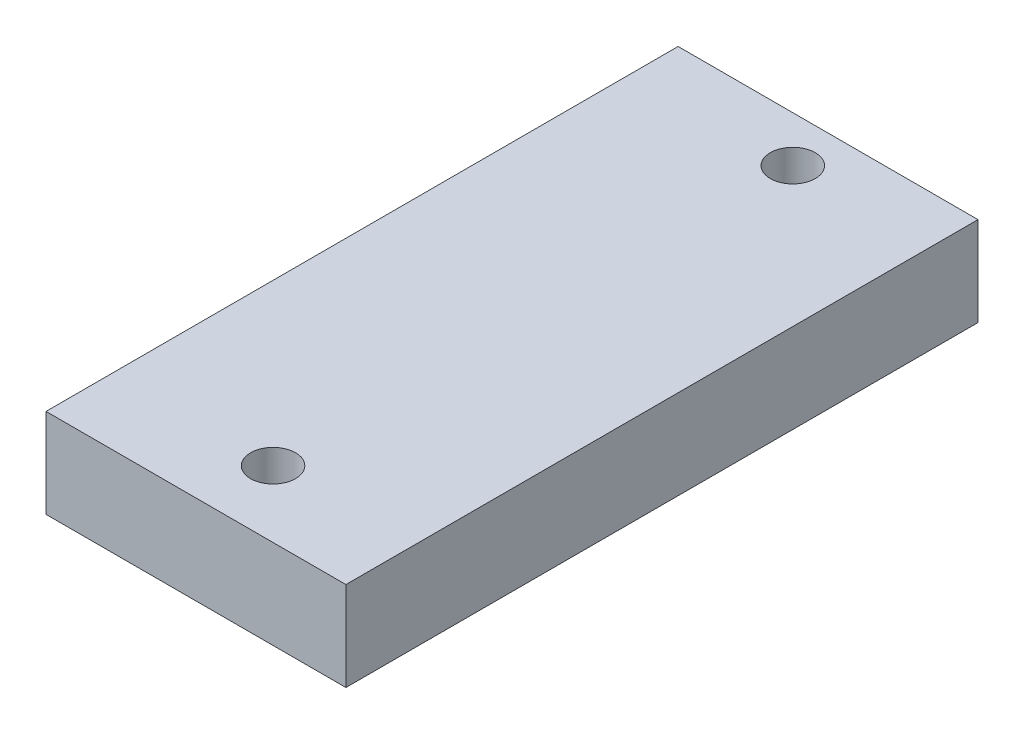
SolidWorks part; units mm, degrees
ref_plane "Front Plane" through (0, 0, 0) normal (0, 0, 1) x (1, 0, 0)
ref_plane "Top Plane" through (0, 0, 0) normal (0, 1, 0) x (1, 0, 0)
ref_plane "Right Plane" through (0, 0, 0) normal (1, 0, 0) x (0, 0, -1)
sketch "Sketch1" plane through (0, 0, 0) normal (0, 1, 0) x (1, 0, 0)
  line L1 (0, 0) -> (21.35, 0)
  line L2 (0, 0) -> (0, 45)
  line L3 (0, 45) -> (21.35, 45)
  line L4 (21.35, 0) -> (21.35, 45)
  dimension "D1" = 45
  dimension "D2" = 21.35
extrude "Boss-Extrude1" add sketch "Sketch1" along normal blind 6.35 contours L2 L3 L4 L1
sketch "Sketch2" plane through (0, 6.35, 0) normal (0, 1, 0) x (1, 0, 0)
  circle A0 centre (11.43, 4.7351) radius 1.6
  circle A1 centre (11.43, 41.7351) radius 1.6
extrude "Cut-Extrude1" cut sketch "Sketch2" against normal blind 10 contours A0
sketch "Sketch3" plane through (0, 6.35, 0) normal (0, 1, 0) x (1, 0, 0)
  circle A0 centre (11.43, 41.7351) radius 1.6
extrude "Cut-Extrude2" cut sketch "Sketch3" against normal blind 10
